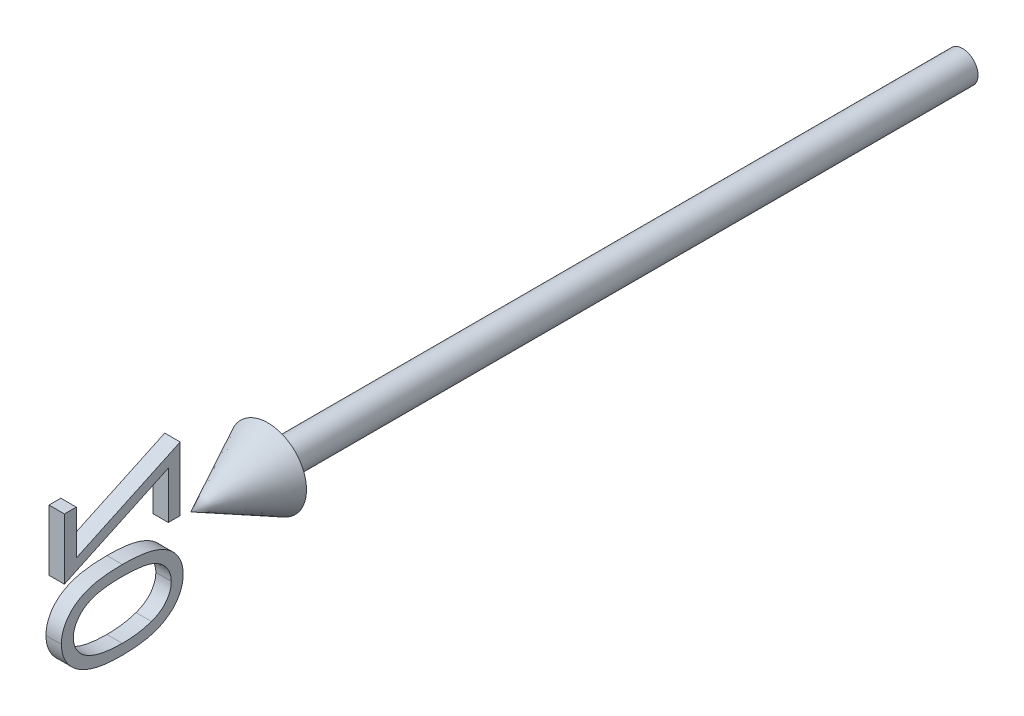
SolidWorks part; units mm, degrees
ref_plane "Front Plane" through (0, 0, 0) normal (0, 0, 1) x (1, 0, 0)
ref_plane "Top Plane" through (0, 0, 0) normal (0, 1, 0) x (1, 0, 0)
ref_plane "Right Plane" through (0, 0, 0) normal (1, 0, 0) x (0, 0, -1)
sketch "Sketch2" plane through (0, 0, 0) normal (0, 1, 0) x (1, 0, 0)
  line L0 (0, 41.95) -> (0, -114.4521) construction
  line L1 (-36.8894, 0) -> (41.4965, 0) construction
  line L2 (0, -100) -> (5, -90)
  line L3 (5, -90) -> (2, -90)
  line L4 (2, -90) -> (2, 0)
  line L5 (2, 0) -> (0, 0)
  line L6 (0, 0) -> (0, -100)
  dimension "D1" = 100
  dimension "D2" = 2
  dimension "D3" = 10
  dimension "D4" = 5
revolve "Revolve1" add sketch "Sketch2" angle 360 about L0
sketch "Sketch3" plane through (0, 0, 0) normal (1, 0, 0) x (0, -1, 0)
  line L0 (0, -101.5706) -> (0, -127.8138) construction
  line L1 (-10.1124, -102.3675) -> (14.1256, -102.3675) construction
  text T0 "Z0" font "Century Gothic" height 15
extrude "Boss-Extrude1" add sketch "Sketch3" against normal blind 1 and the other way blind 1 separate body
equation "\"frame_arrow_length\"=100"
equation "\"D1@Sketch2\"=\"frame_arrow_length\""
equation "\"frame_arrow_odA\"=4"
equation "\"D2@Sketch2\"=\"frame_arrow_odA\"/2"
equation "\"frame_arrow_head_od\"=5"
equation "\"D4@Sketch2\"=\"frame_arrow_head_od\""
equation "\"frame_arrow_head_length\"=10"
equation "\"D3@Sketch2\"=\"frame_arrow_head_length\""
equation "\"tvarobot_theta1\"=30"
equation "\"link0_ringA_odA\"= 40"
equation "\"link0_ringA_odB\"= 25"
equation "\"link0_ringA_id\"= 20"
equation "\"link0_ringA_thickness\"= (\"link0_ringA_odB\" - \"link0_ringA_id\")/2"
equation "\"link0_ringA_height\"= 3"
equation "\"link0_ringA_heightA\"= 1.5"
equation "\"link0_ringA_heightB\"=\"link0_ringA_height\"-\"link0_ringA_heightA\""
equation "\"link0_ringB_odA\"= 40"
equation "\"link0_ringB_odB\"= 29"
equation "\"link0_ringB_id\"= \"link0_shaftA_bearing_id\"+1"
equation "\"link0_ringB_thickness\"= (\"link0_ringB_odB\" - \"link0_ringB_id\")/2"
equation "\"link0_ringB_height\"= 3"
equation "\"link0_ringB_heightA\"= 1.5"
equation "\"link0_ringB_heightB\"=\"link0_ringB_height\"-\"link0_ringB_heightA\""
equation "\"link0_shaftA_bearing_od\"=27"
equation "\"link0_shaftA_bearing_id\"=20"
equation "\"link0_shaftA_thrust_bearing_od\"=35"
equation "\"link0_shaftA_thrust_bearing_id\"=20.04"
equation "\"link0_shaftA_retaining_ring_id\"=18.5"
equation "\"link0_shaftA_retaining_ring_groove_width\"=1.5"
equation "\"link0_shaftA_spline_length\"=8.0"
equation "\"link0_shaftA_spline_depth\"=1.0"
equation "\"link0_shaftA_spline_width\"=4.0"
equation "\"link0_shaftA_odA\"=\"link0_shaftA_bearing_id\""
equation "\"link0_shaftA_odB\"=35"
equation "\"link0_shaftA_odC\"=\"link0_shaftA_bearing_id\""
equation "\"link0_shaftA_odD\"=\"link0_shaftA_odC\"-2*\"link0_shaftA_spline_depth\""
equation "\"link0_shaftA_odE\"=\"link0_shaftA_bearing_id\""
equation "\"link0_shaftA_odF\"=\"link0_shaftA_odE\"-2*\"link0_shaftA_spline_depth\""
equation "\"link0_shaftA_idA\"=10"
equation "\"link0_shaftA_idB\"=6"
equation "\"link0_shaftA_length\"=39.5"
equation "\"link0_shaftA_lengthA\"=8.0"
equation "\"link0_shaftA_lengthB\"=12.0"
equation "\"link0_shaftA_lengthC\"=35.0"
equation "\"link0_shaftA_lengthD\"=39.0"
equation "\"link0_shaftA_lengthE\"=\"link0_shaftA_length\"-\"link0_shaftA_lengthD\""
equation "\"link0_shaftA_offsetX\"=11"
equation "\"link0_shaftA_offsetY\"=0"
equation "\"link0_shaftA_bolt_pattern_dia\"=14"
equation "\"link0_motor_center_dist\"=26"
equation "\"link0_46t_pulley_spline_length\"=8"
equation "\"link0_46t_pulley_spline_depth\"=\"link0_shaftA_spline_depth\"*1.025"
equation "\"link0_46t_pulley_spline_width\"=\"link0_shaftA_spline_width\"*1.05"
equation "\"link0_46t_pulley_idA\"=\"link0_shaftA_bearing_id\"*1.025"
equation "\"link0_46t_pulley_idB\"=\"link0_46t_pulley_idA\"-2*\"link0_46t_pulley_spline_depth\""
equation "\"link0_shaftB_spline_length\"=10"
equation "\"link0_shaftB_spline_depth\"=1.0"
equation "\"link0_shaftB_spline_width\"=1.25"
equation "\"link0_shaftB_length\"=7"
equation "\"link0_shaftB_lengthA\"=1.5"
equation "\"link0_shaftB_lengthB\"=2.75"
equation "\"link0_shaftB_odA\"=32"
equation "\"link0_shaftB_odB\"=22"
equation "\"link0_shaftB_odC\"=20"
equation "\"link0_shaftB_idA\"=10"
equation "\"link0_shaftB_bolt_diameter\"=19"
equation "\"link0_shaftB_bearing_od\"=27"
equation "\"link0_shaftB_bearing_id\"=20"
equation "\"link0_motor_length\"=46.5"
equation "\"link0_motor_width\"=28.5"
equation "\"link0_motor_height\"=34"
equation "\"link0_motor_offset\"=8"
equation "\"link0_shellA_thickness\"=2.5"
equation "\"link0_shellB_thickness\"=\"link0_shellA_thickness\""
equation "\"link0_plateA_shellA_height\"=48"
equation "\"link0_shellA_width\" =\"link0_plateA_width\""
equation "\"link0_shellA_height\" = \"link0_plateA_shellA_height\"-\"link0_plateA_height\""
equation "\"link0_shellA_length\" = \"link0_plateA_lengthB\" "
equation "\"link0_shellB_length\"=\"link0_shellA_length\""
equation "\"link0_shellA_radius\" = 0.375*25.4"
equation "\"link0_shellA_radiusA\"= \"link0_plateA_radiusA\""
equation "\"link0_shellA_radiusB\"= \"link0_plateA_radiusB\""
equation "\"link0_shellA_radiusC\"= 3"
equation "\"link0_postA_height\"=7"
equation "\"link0_postA_width\"=16"
equation "\"link0_postA_length\"=20"
equation "\"link0_postA_posX\"=22"
equation "\"link0_postA_posY\"=17.5"
equation "\"link0_postA_pocket_width\"=6.0"
equation "\"link0_postA_pocket_length\"=2.5"
equation "\"link0_postA_pocket_depth\"=9"
equation "\"link0_postA_pocket_posZ\"=10"
equation "\"link0_postB_height\"=7"
equation "\"link0_postB_width\"=16"
equation "\"link0_postB_length\"=20"
equation "\"link0_postB_posX\"=22"
equation "\"link0_postB_posY\"=17.5"
equation "\"link0_postB_id\"=3.0"
equation "\"link0_postB_pocket_width\"=6.0"
equation "\"link0_postB_pocket_length\"=2.5"
equation "\"link0_postB_pocket_depth\"=9"
equation "\"link0_postB_pocket_posZ\"=10"
equation "\"link0_postC_height\"=7"
equation "\"link0_postC_width\"=16"
equation "\"link0_postC_length\"=20"
equation "\"link0_postC_posX\"=22"
equation "\"link0_postC_posY\"=17.5"
equation "\"link0_postC_id\"=3.0"
equation "\"link0_postC_pocket_width\"=6.0"
equation "\"link0_postC_pocket_length\"=2.5"
equation "\"link0_postC_pocket_depth\"=9"
equation "\"link0_postC_pocket_posZ\"=10"
equation "\"link0_postD_height\"=7"
equation "\"link0_postD_width\"=16"
equation "\"link0_postD_length\"=20"
equation "\"link0_postD_posX\"=22"
equation "\"link0_postD_posY\"=17.5"
equation "\"link0_postD_id\"=3.0"
equation "\"link0_postD_pocket_width\"=6.0"
equation "\"link0_postD_pocket_length\"=3.0"
equation "\"link0_postD_pocket_depth\"=9"
equation "\"link0_postD_pocket_posZ\"=10"
equation "\"link0_postE_height\"=5"
equation "\"link0_postE_width\"=16"
equation "\"link0_postE_length\"=\"link0_plateE_lengthA\"-\"link0_lip_height\""
equation "\"link0_postE_posZ\"=22"
equation "\"link0_postE_posX\"=17.5"
equation "\"link0_postE_posY\"=22"
equation "\"link0_postE_id\"=3.0"
equation "\"link0_postE_cbore_id\"=6.5"
equation "\"link0_postE_hole_id\"=3"
equation "\"link0_postF_posZ\"=22"
equation "\"link0_postF_posX\"=17.5"
equation "\"link0_postF_posY\"=\"link0_plateB_lengthA\"+4"
equation "\"link0_postF_id\"=3.0"
equation "\"link0_postF_cbore_id\"=6.5"
equation "\"link0_postF_hole_id\"=3"
equation "\"link0_postG_posZ\"=22"
equation "\"link0_postG_posX\"=17.5"
equation "\"link0_postG_posY\"=\"link0_plateB_lengthA\"+12"
equation "\"link0_postG_id\"=3.0"
equation "\"link0_postG_cbore_id\"=6.5"
equation "\"link0_postG_hole_id\"=3"
equation "\"link0_postHIJ_posY\"=6"
equation "\"link0_postH_posX\"=28"
equation "\"link0_postH_posY\"=20"
equation "\"link0_postH_posZ\"=20"
equation "\"link0_postH_length\"=10"
equation "\"link0_postI_posX\"=28"
equation "\"link0_postI_posY\"=20"
equation "\"link0_postI_posZ\"=135"
equation "\"link0_postI_length\"=10"
equation "\"link0_postJ_posX\"=28"
equation "\"link0_postJ_posY\"=20"
equation "\"link0_postJ_posZ\"=175"
equation "\"link0_postJ_length\"=10"
equation "\"link0_postK_posX\"=28"
equation "\"link0_postK_posY\"=20"
equation "\"link0_postK_posZ\"=175"
equation "\"link0_postK_length\"=10"
equation "\"link0_postL_posX\"=28"
equation "\"link0_postL_posY\"=20"
equation "\"link0_postL_posZ\"=135"
equation "\"link0_postL_length\"=10"
equation "\"link0_postM_posX\"=28"
equation "\"link0_postM_posY\"=20"
equation "\"link0_postM_posZ\"=35"
equation "\"link0_postM_length\"=10"
equation "\"link0_plateA_lengthA\"=30"
equation "\"link0_plateA_lengthB\"=150"
equation "\"link0_plateA_lengthC\"=30"
equation "\"link0_plateA_length\"=\"link0_plateA_lengthA\"+\"link0_plateA_lengthB\"+\"link0_plateA_lengthC\""
equation "\"link0_plateA_width\"=  68"
equation "\"link0_plateA_height\"= \"link0_plateA_radiusA\""
equation "\"link0_plateA_thickness\"=\"link0_shellA_thickness\""
equation "\"link0_plateA_radius\"= 9.5"
equation "\"link0_plateA_radiusA\"= 18"
equation "\"link0_plateA_radiusB\"= 18"
equation "\"link0_plateA_radiusC\"= 3"
equation "\"link0_plateB_length\"= 40"
equation "\"link0_plateB_width\"= \"link0_plateA_width\"*1.005"
equation "\"link0_plateB_height\"= \"link0_plateA_shellA_height\"*1.005"
equation "\"link0_plateB_lengthA\"=\"link0_lip_height\"+\"link0_plateD_thickness\"+\"link0_motor_mount_thickness\""
equation "\"link0_plateB_lengthB\"=\"link0_plateB_height\"-\"link0_plateB_lengthA\""
equation "\"link0_plateB_radiusA\"= \"link0_plateA_radiusA\""
equation "\"link0_plateB_radiusB\"= \"link0_plateA_radiusB\""
equation "\"link0_plateB_radiusC\"= 3"
equation "\"link0_plateB_idA\"=\"link0_shaftA_odC\"+1"
equation "\"link0_plateB_idB\"=\"link0_shaftA_bearing_od\"-2"
equation "\"link0_plateB_idC\"=\"link0_shaftA_bearing_od\"*1.005"
equation "\"link0_plateB_idD\"=\"link0_shaftA_thrust_bearing_od\"+1 "
equation "\"link0_plateB_depthA\"=1.0"
equation "\"link0_plateB_depthB\"=2.0"
equation "\"link0_plateB_depthC\"=8"
equation "\"link0_plateB_depthD\"=\"link0_plateB_length\"-\"link0_lip_height\"-\"link0_plateD_thickness\" "
equation "\"link0_plateC_length\"=\"link0_plateB_length\""
equation "\"link0_plateC_width\"= \"link0_plateB_width\""
equation "\"link0_plateC_height\"= .1*25.4"
equation "\"link0_plateA_hole_od\" = 0.1*25.4"
equation "\"link0_plateA_hole_delx\" = 0.5*25.4"
equation "\"link0_plateA_hole_delz\" = 0.75*25.4"
equation "\"link0_plateA_hole_offx\" = 0.0*25.4"
equation "\"link0_plateA_hole_offz\" = \"link0_plateA_length\"/2"
equation "\"link0_plateB_hole_od\" = 0.1*25.4"
equation "\"link0_plateB_hole_delx\"= 0.75*25.4"
equation "\"link0_plateB_hole_delz\"= 0.75*25.4"
equation "\"link0_plateB_hole_offx\"= 0.0*25.4"
equation "\"link0_plateB_hole_offz\"= 0.0*25.4"
equation "\"link0_plateC_hole_od\"= 0.1*25.4"
equation "\"link0_plateC_hole_delx\"= 0.75*25.4"
equation "\"link0_plateC_hole_delz\"= 0.75*25.4"
equation "\"link0_plateC_hole_offx\"= 0.0*25.4"
equation "\"link0_plateC_hole_offz\"= 0.0*25.4"
equation "\"link0_plateD_height\"=\"link0_plateB_height\"-2*\"link0_shellA_thickness\""
equation "\"link0_plateD_width\"=\"link0_plateB_width\"-2*\"link0_shellA_thickness\""
equation "\"link0_plateD_thickness\"=10"
equation "\"link0_plateD_radiusA\"=\"link0_plateB_radiusA\"-\"link0_shellA_thickness\""
equation "\"link0_plateD_odA\"= .375*25.4"
equation "\"link0_plateD_odB\"= .375*25.4"
equation "\"link0_plateD_bearing_id\"=20"
equation "\"link0_plateD_bearing_od\"=27"
equation "\"link0_plateE_radiusA\"=\"link0_plateA_radiusA\""
equation "\"link0_plateE_radiusB\"=\"link0_plateA_radiusB\""
equation "\"link0_plateE_radiusC\"=8.0"
equation "\"link0_plateE_length\"=30"
equation "\"link0_plateE_lengthA\"=16"
equation "\"link0_plateE_height\"=\"link0_plateB_height\""
equation "\"link0_plateE_width\"=\"link0_plateB_width\""
equation "\"link0_plateE_odA\"=\"gantry_coupler_id\"*0.99"
equation "\"link0_plateE_idA\"=\"link0_plateE_odA\"-20.0"
equation "\"link0_plateE_spline_depth\"=\"link0_poleA_spline_depth\"*1.05"
equation "\"link0_plateE_spline_width\"=\"link0_poleA_spline_width\"*1.075"
equation "\"link0_plateE_spline_length\"=\"link0_poleA_spline_length\""
equation "\"link0_plateE_coupler_length\"=46"
equation "\"link0_lip_height\"=5.0"
equation "\"link0_lip_thickness\"=2.0"
equation "\"link0_motor_mount_thickness\"=8.0"
equation "\"link0_motor_mount_idA\"=22"
equation "\"link0_motor_mount_idB\"=\"link0_shaftB_bearing_od\"*1.005"
equation "\"link0_motor_mount_idC\"=\"link0_shaftB_bearing_od\"-2"
equation "\"link0_motor_mount_depthA\"=5.5"
equation "\"link0_motor_mount_height\"=\"link0_plateD_height\""
equation "\"link0_motor_mount_width\"=\"link0_plateD_width\""
equation "\"link0_motor_mountL_height\"=36"
equation "\"link0_motor_mountL_heightA\"=12"
equation "\"link0_motor_mountL_length\"=50"
equation "\"link0_motor_mountL_lengthA\"=36"
equation "\"gantry_coupler_od\"=25.4*2.0"
equation "\"gantry_coupler_id\"=1.645*25.4"
equation "\"gantry_coupler_offsetX\"=\"link0_plateE_width\"/2"
equation "\"link0_poleA_odA\"=20"
equation "\"link0_poleA_odB\"=36"
equation "\"link0_poleA_idA\"=\"link0_poleA_odA\"-2*\"link0_poleA_thickness\""
equation "\"link0_poleA_idB\"=(\"link0_plateE_idA\"/2+1.5*\"link0_lip_thickness\")*1.04"
equation "\"link0_poleA_thickness\"=3.5"
equation "\"link0_poleA_length\"=100"
equation "\"link0_poleA_lengthA\"=18.5"
equation "\"link0_poleA_lengthB\"=80"
equation "\"link0_poleA_gasket_thickness\"=1.5"
equation "\"link0_poleA_spline_depth\"=1.0"
equation "\"link0_poleA_spline_width\"=4.0"
equation "\"link0_poleA_spline_length\"=10.0"
equation "\"link1_plateB_length\"=30"
equation "\"link1_lip_height\"=\"link0_lip_height\""
equation "\"link0_tension_plateA_width\"=12"
equation "\"link0_tension_plateA_lengthA\"=10.5"
equation "\"link0_tension_plateB_width\"=\"link0_tension_plateA_width\""
equation "\"link0_tension_plateB_lengthA\"=\"link0_tension_plateA_lengthA\""
equation "\"link0_tension_wheelA_posZ\"=7"
equation "\"link0_tension_wheelA_posX\"=\"link0_plateD_height\"/2-\"link0_tension_plateA_lengthA\""
equation "\"link0_m2_clear_hole_id\"=2.35"
equation "\"link0_m2_insert_hole_id\"=2.5"
equation "\"link0_m2_tap_hole_id\"=1.75"
equation "\"link0_m2_nut_socket_width\"=4.25"
equation "\"link0_m2_nut_socket_depth\"=2.5"
equation "\"link0_m2_cbore_id\"=3.75"
equation "\"link0_m2_cbore_depth\"=7"
equation "\"link0_m2_5_clear_hole_id\"=2.75"
equation "\"link0_m2_5_insert_hole_id\"=2.75"
equation "\"link0_m2_5_tap_hole_id\"=2.25"
equation "\"link0_m2_5_nut_socket_width\"=5.25"
equation "\"link0_m2_5_nut_socket_depth\"=2.5"
equation "\"link0_m2_5_cbore_id\"=4.75"
equation "\"link0_m2_5_cbore_depth\"=2.5"
equation "\"link0_m2_5_insert_access_length\"=6.0"
equation "\"link0_m2_5_insert_access_width\"=3.0"
equation "\"link0_m3_clear_hole_id\"=3.25"
equation "\"link0_m3_insert_hole_id\"=3"
equation "\"link0_m3_tap_hole_id\"=2.75"
equation "\"link0_m3_nut_socket_width\"=5.75"
equation "\"link0_m3_nut_socket_depth\"=4.0"
equation "\"link0_m3_cbore_id\"=5.75"
equation "\"link0_m3_cbore_depth\"=3.5"
equation "\"link0_m3_insert_access_length\"=4.5"
equation "\"link0_m3_insert_access_width\"=3.5"
equation "\"link0_rpi_mount_height\"=6"
equation "\"link0_rpi_mount_width\"=49"
equation "\"link0_rpi_mount_length\"=58"
equation "\"link0_rpi_mount_post_od\"=6"
equation "\"link0_rpi_mount_posZ\"=72"
equation "\"link0_rpi_mount_posX\"=11.5"
equation "\"link0_mcu_mount_height\"=5"
equation "\"link0_mcu_mount_width\"=49"
equation "\"link0_mcu_mount_length\"=58"
equation "\"link0_mcu_mount_post_od\"=6"
equation "\"link0_mcu_mount_posZ\"=164"
equation "\"link0_mcu_mount_posX\"=4"
equation "\"link0_pwr_mount_height\"=4"
equation "\"link0_pwr_mount_width\"=15.75"
equation "\"link0_pwr_mount_length\"=75.75"
equation "\"link0_pwr_mount_post_od\"=6"
equation "\"link0_pwr_mount_posZ\"=75"
equation "\"link0_pwr_mount_posX\"=16"
equation "\"link0_pwr_board_height\"=6"
equation "\"link0_pwr_board_width\"=21"
equation "\"link0_pwr_board_length\"=80"
